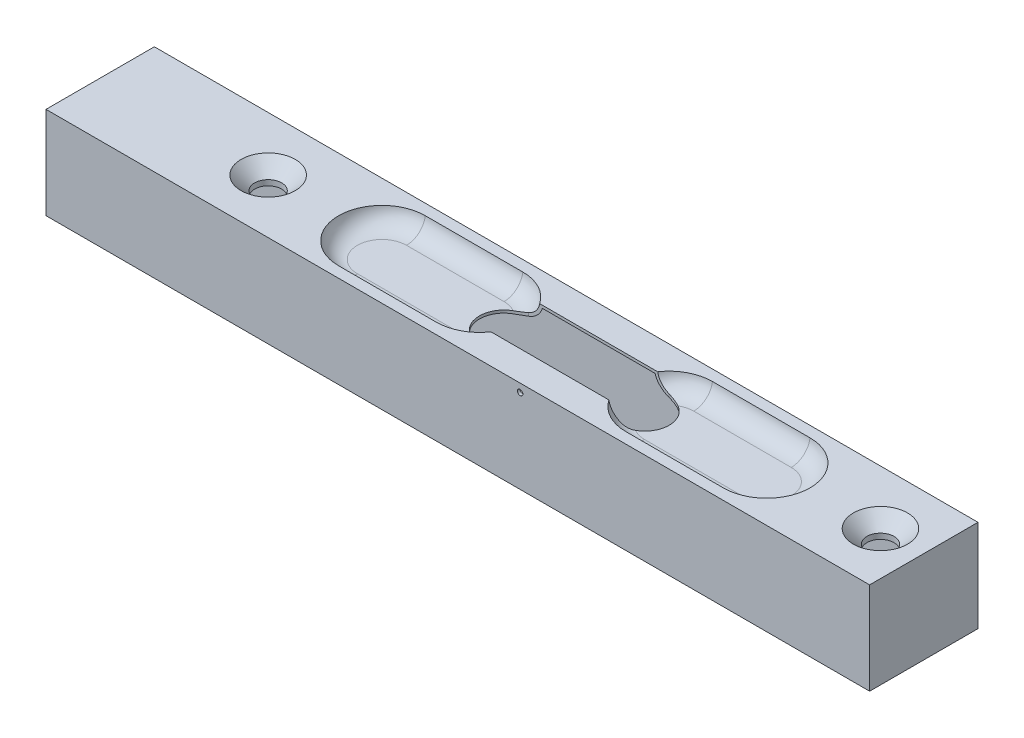
SolidWorks part; units mm, degrees
material "Stainless Steel (ferritic)"
ref_plane "Front Plane" through (0, 0, 0) normal (0, 0, 1) x (1, 0, 0)
ref_plane "Top Plane" through (0, 0, 0) normal (0, 1, 0) x (1, 0, 0)
ref_plane "Right Plane" through (0, 0, 0) normal (1, 0, 0) x (0, 0, -1)
sketch "Sketch1" plane through (0, 0, 0) normal (0, 1, 0) x (1, 0, 0)
  line L1 (-76, -10) -> (76, -10)
  line L2 (-76, -10) -> (-76, 10)
  line L3 (-76, 10) -> (76, 10)
  line L4 (76, -10) -> (76, 10)
  line L5 (-76, -10) -> (76, 10) construction
  line L6 (-76, 10) -> (76, -10) construction
  point P0 (0, 0)
  dimension "D1" = 20
  dimension "D2" = 152
extrude "Boss-Extrude1" add sketch "Sketch1" along normal blind 17
sketch "Sketch2" plane through (0, 17, 0) normal (0, 1, 0) x (1, 0, 0)
  line L0 (-45, 0) -> (68, 0) construction
  line L1 (-76, 10) -> (-76, -10) construction
  line L2 (76, -10) -> (76, 10) construction
  line L3 (-24, 0) -> (-6, 0) construction
  line L4 (-24, 8) -> (-6, 8)
  line L5 (-24, -8) -> (-6, -8)
  line L6 (29, 0) -> (47, 0) construction
  line L7 (29, 8) -> (47, 8)
  line L8 (29, -8) -> (47, -8)
  line L10 (-472.4182, 183.3202) -> (-320.4182, 183.3202) construction
  circle A0 centre (68, 0) radius 2.5
  circle A1 centre (-45, 0) radius 2.5
  arc A2 (-24, 8) -> (-24, -8) centre (-24, 0) ccw
  arc A3 (-6, -8) -> (-6, 8) centre (-6, 0) ccw
  arc A4 (29, 8) -> (29, -8) centre (29, 0) ccw
  arc A5 (47, -8) -> (47, 8) centre (47, 0) ccw
  point P11 (-15, 0)
  point P16 (38, 0)
  point P25 (-32, 0)
  point P26 (2, 0)
  dimension "D2" = 8
  dimension "D3" = 5
  dimension "D1" = 31
  dimension "D4" = 16
  dimension "D5" = 21
  dimension "D6" = 34
  dimension "D7" = 152
  dimension "D8" = 21
  dimension "D9" = 53
extrude "Cut-Extrude1" cut sketch "Sketch2" against normal blind 3
fillet "Fillet1" radius 3.5 8 edges at (55, 14, 0) (38, 14, 8) (21, 14, 0) (2, 14, 0) (-15, 14, 8) (-32, 14, 0) (38, 14, -8) (-15, 14, -8)
chamfer "Chamfer1" distance 2.5 angle 45 2 edges at (68, 17, 2.5) (-45, 17, 2.5)
shell "Shell1" thickness 0.5 removed face at (0, 0, 0)
sketch "Sketch3" plane through (0, 0, 0) normal (0, 1, 0) x (1, 0, 0)
  line L0 (-1.5, 0) -> (24.5, 0) construction
  line L1 (-45, 0) -> (68, 0) construction
  line L2 (-1.5, 4.5) -> (24.5, 4.5)
  line L3 (-1.5, -4.5) -> (24.5, -4.5)
  line L4 (-45, 0) -> (68, 0) construction
  circle A0 centre (-45, 0) radius 2.5
  circle A1 centre (68, 0) radius 2.5
  circle A2 centre (-45, 0) radius 2.5 construction
  circle A3 centre (68, 0) radius 2.5 construction
  arc A4 (-1.5, 4.5) -> (-1.5, -4.5) centre (-1.5, 0) ccw
  arc A5 (24.5, -4.5) -> (24.5, 4.5) centre (24.5, 0) ccw
  point P14 (11.5, 0)
  point P23 (11.5, 0)
  dimension "D1" = 26
  dimension "D2" = 9
extrude "Cut-Extrude2" cut sketch "Sketch3" along normal through all
sketch "Sketch4" plane through (-76, 0, 0) normal (-1, 0, 0) x (0, 0, 1)
  line L0 (-10, 17) -> (10, 0) construction
  circle A0 centre (0, 8.5) radius 5.25
  dimension "D1" = 10.5
extrude "Cut-Extrude3" cut sketch "Sketch4" against normal up to next
sketch "Sketch5" plane through (0, 0, 0) normal (0, 0, 1) x (1, 0, 0)
  line L0 (2, 17) -> (21, 17) construction
  line L1 (2, 17) -> (-6, 17) construction
  line L2 (-45, 17) -> (68, 17) construction
  line L3 (29, 17) -> (21, 17) construction
  line L4 (11.5, 17) -> (11.5, 15.5) construction
  circle A0 centre (11.5, 15.5) radius 0.5
  dimension "D1" = 1
  dimension "D2" = 1.5
extrude "Cut-Extrude4" cut sketch "Sketch5" against normal through all both and the other way through all
